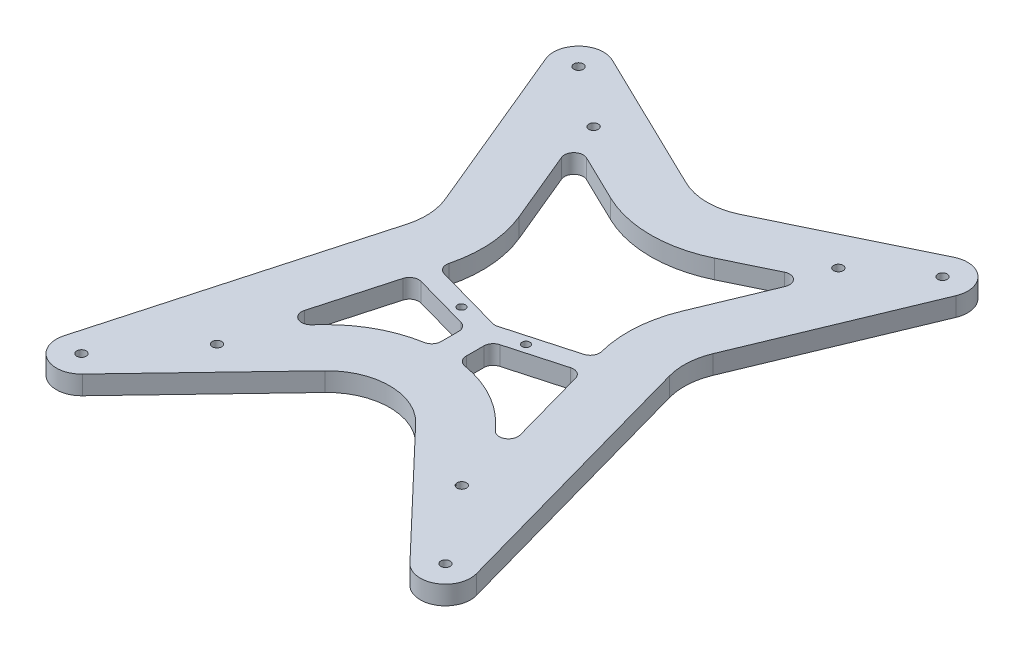
SolidWorks part; units mm, degrees
material "1060 Alloy"
ref_plane "Front Plane" through (0, 0, 0) normal (0, 0, 1) x (1, 0, 0)
ref_plane "Top Plane" through (0, 0, 0) normal (0, 1, 0) x (1, 0, 0)
ref_plane "Right Plane" through (0, 0, 0) normal (1, 0, 0) x (0, 0, -1)
sketch "Sketch1" plane through (0, 0, 0) normal (0, 1, 0) x (1, 0, 0)
  line L0 (-54.4954, 86.3958) -> (0, 60)
  line L1 (0, 60) -> (54.4954, 86.3958)
  line L2 (65.3716, 76.1292) -> (40, 15)
  line L3 (40, 15) -> (65.6883, -77.0455)
  line L4 (52.194, -84.7177) -> (0, -30)
  line L5 (0, -30) -> (-52.194, -84.7177)
  line L6 (-65.6883, -77.0455) -> (-40, 15)
  line L7 (-40, 15) -> (-65.3716, 76.1292)
  line L8 (-68.5894, 68.5894) -> (68.5894, -68.5894) construction
  line L9 (-42, 75) -> (-36, 75) construction
  line L10 (-42, 75) -> (-42, 55) construction
  line L11 (-42, 55) -> (-36, 55) construction
  line L12 (-36, 75) -> (-36, 55) construction
  line L13 (-42, 75) -> (-36, 55) construction
  line L14 (-42, 55) -> (-36, 75) construction
  line L15 (36, 75) -> (42, 75) construction
  line L16 (36, 75) -> (36, 55) construction
  line L17 (36, 55) -> (42, 55) construction
  line L18 (42, 75) -> (42, 55) construction
  line L19 (36, 75) -> (42, 55) construction
  line L20 (36, 55) -> (42, 75) construction
  line L21 (36, -45) -> (42, -45) construction
  line L22 (36, -45) -> (36, -65) construction
  line L23 (36, -65) -> (42, -65) construction
  line L24 (42, -45) -> (42, -65) construction
  line L25 (36, -45) -> (42, -65) construction
  line L26 (36, -65) -> (42, -45) construction
  line L27 (-42, -45) -> (-36, -45) construction
  line L28 (-42, -45) -> (-42, -65) construction
  line L29 (-42, -65) -> (-36, -65) construction
  line L30 (-36, -45) -> (-36, -65) construction
  line L31 (-42, -45) -> (-36, -65) construction
  line L32 (-42, -65) -> (-36, -45) construction
  line L33 (97, 40.1787) -> (40.1787, 97) construction
  line L34 (40.1787, 97) -> (-40.1787, 97) construction
  line L35 (-40.1787, 97) -> (-97, 40.1787) construction
  line L36 (-97, 40.1787) -> (-97, -40.1787) construction
  line L37 (-97, -40.1787) -> (-40.1787, -97) construction
  line L38 (-40.1787, -97) -> (40.1787, -97) construction
  line L39 (40.1787, -97) -> (97, -40.1787) construction
  line L40 (97, -40.1787) -> (97, 40.1787) construction
  line L41 (68.5894, 68.5894) -> (-68.5894, -68.5894) construction
  circle A0 centre (-57.9828, 79.196) radius 1.5
  circle A1 centre (57.9828, 79.196) radius 1.5
  circle A2 centre (-57.9828, -79.196) radius 1.5
  circle A3 centre (57.9828, -79.196) radius 1.5
  arc A4 (-54.4954, 86.3958) -> (-65.3716, 76.1292) centre (-57.9828, 79.196) ccw
  arc A5 (54.4954, 86.3958) -> (65.3716, 76.1292) centre (57.9828, 79.196) cw
  arc A6 (-65.6883, -77.0455) -> (-52.194, -84.7177) centre (-57.9828, -79.196) ccw
  arc A7 (65.6883, -77.0455) -> (52.194, -84.7177) centre (57.9828, -79.196) cw
  circle A8 centre (0, 0) radius 97 construction
  circle A9 centre (-39, 65) radius 1.5
  circle A10 centre (39, 65) radius 1.5
  circle A11 centre (39, -55) radius 1.5
  circle A12 centre (-39, -55) radius 1.5
  ellipse E0 centre (0, 15) end of major axis (0, 60) minor radius 40 construction
  dimension "D5" = 3
  dimension "D6" = 45
  dimension "D7" = 8
  dimension "D12" = 3
  dimension "D3" = 15
  dimension "D4" = 15
  dimension "D8" = 120
  dimension "D9" = 78
  dimension "D10" = 15
  dimension "D11" = 55
  dimension "D13" = 40
  dimension "D14" = 39
  dimension "D15" = 20
  dimension "D16" = 6
  dimension "D17" = 97
  dimension "D18" = 15
extrude "Boss-Extrude1" add sketch "Sketch1" along normal blind 6
fillet "Fillet1" radius 20 4 edges at (0, 3, -60) (-40, 3, -15) (0, 3, 30) (40, 3, -15)
sketch "Sketch2" plane through (0, 6, 0) normal (0, 1, 0) x (1, 0, 0)
  line L44 (-38.6591, 58.7249) -> (-26.025, 28.2848)
  line L45 (-24.5208, 3.5031) -> (-37.5911, -43.3302)
  line L46 (-37.5911, -43.3302) -> (-27.4967, -32.7477)
  line L47 (27.4967, -32.7477) -> (37.5911, -43.3302)
  line L48 (37.5911, -43.3302) -> (24.5208, 3.5031)
  line L49 (26.025, 28.2848) -> (38.6591, 58.7249)
  line L50 (38.6591, 58.7249) -> (16.5651, 48.0232)
  line L51 (-16.5651, 48.0232) -> (-38.6591, 58.7249)
  line L52 (-38.6591, 58.7249) -> (-26.025, 28.2848)
  line L53 (-24.5208, 3.5031) -> (-37.5911, -43.3302)
  line L54 (-37.5911, -43.3302) -> (-27.4967, -32.7477)
  line L55 (27.4967, -32.7477) -> (37.5911, -43.3302)
  line L56 (37.5911, -43.3302) -> (24.5208, 3.5031)
  line L57 (26.025, 28.2848) -> (38.6591, 58.7249)
  line L58 (38.6591, 58.7249) -> (16.5651, 48.0232)
  line L59 (-16.5651, 48.0232) -> (-38.6591, 58.7249)
  arc A40 (-24.5208, 3.5031) -> (-26.025, 28.2848) centre (-61.1221, 13.7179) ccw
  arc A41 (27.4967, -32.7477) -> (-27.4967, -32.7477) centre (0, -58.9762) ccw
  arc A42 (26.025, 28.2848) -> (24.5208, 3.5031) centre (61.1221, 13.7179) ccw
  arc A43 (-16.5651, 48.0232) -> (16.5651, 48.0232) centre (0, 82.2226) ccw
  arc A44 (-24.5208, 3.5031) -> (-26.025, 28.2848) centre (-61.1221, 13.7179) ccw
  arc A45 (27.4967, -32.7477) -> (-27.4967, -32.7477) centre (0, -58.9762) ccw
  arc A46 (26.025, 28.2848) -> (24.5208, 3.5031) centre (61.1221, 13.7179) ccw
  arc A47 (-16.5651, 48.0232) -> (16.5651, 48.0232) centre (0, 82.2226) ccw
  dimension "D1" = 18
extrude "Cut-Extrude1" cut sketch "Sketch2" against normal up to next
sketch "Sketch5" plane through (0, 6, 0) normal (0, 1, 0) x (1, 0, 0)
  line L0 (-25.1032, 1.416) -> (0, -5.5899)
  line L1 (-12.94, -8.43) -> (12.94, -8.43) construction
  line L2 (-12.94, -8.43) -> (-12.94, 8.43) construction
  line L3 (-12.94, 8.43) -> (12.94, 8.43) construction
  line L4 (12.94, -8.43) -> (12.94, 8.43) construction
  line L5 (-12.94, -8.43) -> (12.94, 8.43) construction
  line L6 (-12.94, 8.43) -> (12.94, -8.43) construction
  line L7 (-24.5208, 3.5031) -> (-37.5911, -43.3302) construction
  line L8 (0, -5.5899) -> (25.1032, 1.416)
  line L9 (37.5911, -43.3302) -> (24.5208, 3.5031) construction
  line L10 (25.1032, 1.416) -> (26.7161, -4.3632)
  line L11 (26.7161, -4.3632) -> (4, -10.7029)
  line L12 (4, -10.7029) -> (4, -21.1873)
  line L13 (-4, -21.1873) -> (-4, -10.7029)
  line L14 (-4, -10.7029) -> (-26.7161, -4.3632)
  line L15 (-26.7161, -4.3632) -> (-25.1032, 1.416)
  circle A0 centre (-10.3, -5.83) radius 1.25
  circle A1 centre (10.3, -5.83) radius 1.25
  arc A2 (27.4967, -32.7477) -> (-27.4967, -32.7477) centre (0, -58.9762) ccw construction
  arc A3 (4, -21.1873) -> (-4, -21.1873) centre (0, -58.9762) ccw
  point P0 (0, 0)
  dimension "D3" = 2.5
  dimension "D1" = 16.86
  dimension "D2" = 25.88
  dimension "D4" = 20.6
  dimension "D5" = 2.64
  dimension "D6" = 2.6
  dimension "D7" = 6
  dimension "D8" = 3
  dimension "D9" = 8
extrude "Boss-Extrude2" add sketch "Sketch5" against normal up to surface (6 mm away) up to face at (0, 0, -11.095)
fillet "Fillet2" radius 3 13 edges at (37.5911, 3, 43.3302) (-37.5911, 3, 43.3302) (38.6591, 3, -58.7249) (-38.6591, 3, -58.7249) (25.1032, 3, -1.416) (-25.1032, 3, -1.416) (0, 3, 5.5899) (26.7161, 3, 4.3632) (4, 3, 10.7029) (4, 3, 21.1873) (-4, 3, 21.1873) (-4, 3, 10.7029) (-26.7161, 3, 4.3632)
equation "\"D14@Sketch1\"=\"D9@Sketch1\"/2"
